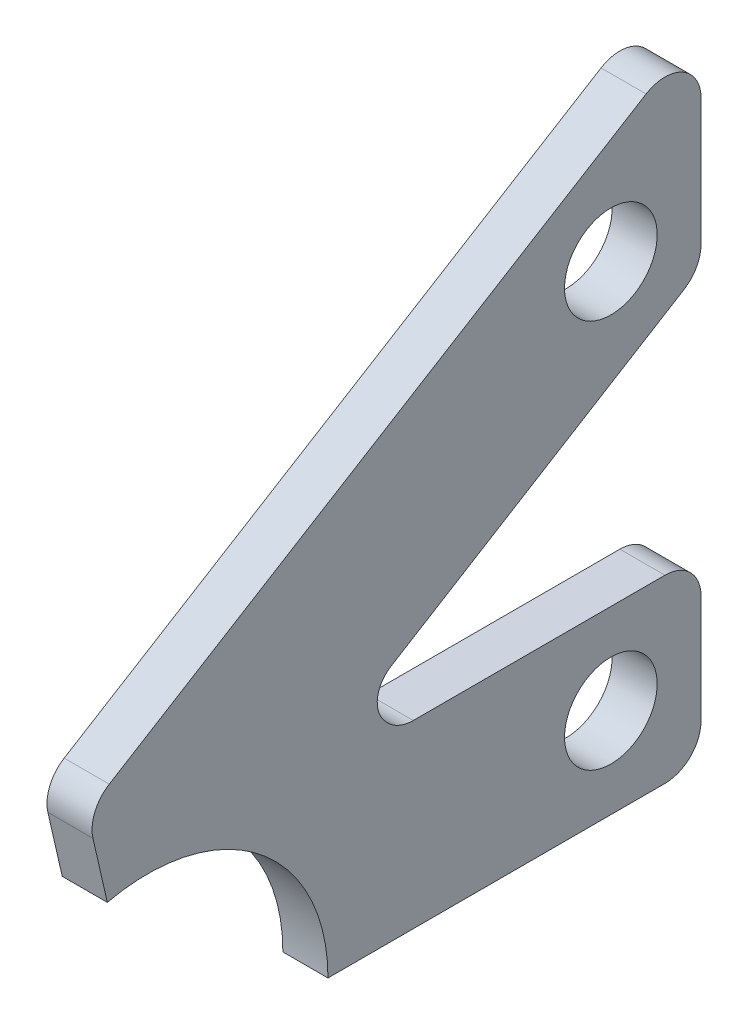
SolidWorks part; units mm, degrees
material "AISI 4130 Steel, annealed at 865C"
ref_plane "Front Plane" through (0, 0, 0) normal (0, 0, 1) x (1, 0, 0)
ref_plane "Top Plane" through (0, 0, 0) normal (0, 1, 0) x (1, 0, 0)
ref_plane "Right Plane" through (0, 0, 0) normal (1, 0, 0) x (0, 0, -1)
sketch "Sketch2" plane through (-112.555, 0, -573.5897) normal (-1, 0, 0) x (0, 0.6231, 0.7821)
  line L0 (845.7718, 136.9996) -> (864.3306, 122.2137)
  line L1 (871.0899, 172.8543) -> (811.2713, 97.7721) construction
  line L2 (864.3306, 122.2137) -> (884.1965, 122.2137) construction
  line L3 (884.1965, 122.2137) -> (887.7358, 125.0335)
  line L4 (853.6855, 146.9326) -> (867.5451, 135.8905)
  line L5 (888.541, 127.8859) -> (873.4237, 169.576)
  line L6 (871.3239, 138.1115) -> (863.0777, 160.8527)
  line L7 (845.3679, 140.569) -> (850.1161, 146.5287)
  line L8 (863.479, 163.3013) -> (869.0493, 170.2929)
  line L9 (852.7085, 139.592) -> (869.7744, 161.0125) construction
  circle A0 centre (874.2635, 114.3) radius 12.7 construction
  arc A1 (864.3306, 122.2137) -> (884.1965, 122.2137) centre (874.2635, 114.3) cw
  arc A2 (887.7358, 125.0335) -> (888.541, 127.8859) centre (886.1531, 127.0201) ccw
  circle A3 centre (852.7085, 139.592) radius 3.2639
  circle A4 centre (869.7744, 161.0125) radius 3.2639
  arc A6 (869.8308, 135.4301) -> (869.6684, 135.3953) centre (874.2635, 114.3) ccw
  arc A7 (845.7718, 136.9996) -> (845.3679, 140.569) centre (847.3545, 138.9862) cw
  arc A8 (853.6855, 146.9326) -> (850.1161, 146.5287) centre (852.1027, 144.946) ccw
  arc A9 (869.0493, 170.2929) -> (873.4237, 169.576) centre (871.0358, 168.7102) cw
  arc A10 (863.0777, 160.8527) -> (863.479, 163.3013) centre (865.4656, 161.7186) cw
  arc A11 (867.5451, 135.8905) -> (869.6684, 135.3953) centre (869.1278, 137.8771) ccw
  arc A12 (871.3239, 138.1115) -> (869.8308, 135.4301) centre (869.4136, 137.4188) cw
  point P17 (889.163, 126.1705)
  point P25 (843.7852, 138.5824)
  point P28 (851.6989, 148.5153)
  point P31 (871.8768, 173.842)
  point P34 (862.593, 162.1893)
  dimension "D5" = 2.54
  dimension "D10" = 6.5278
  dimension "D9" = 2.54
  dimension "D4" = 8.89
  dimension "D12" = 2.54
  dimension "D13" = 2.54
  dimension "D14" = 2.54
  dimension "D15" = 2.54
  dimension "D16" = 2.032
  dimension "D1" = 12.7
  dimension "D2" = 12.7
  dimension "D3" = 6.35
  dimension "D7" = 6.35
  dimension "D8" = 6.35
  dimension "D11" = 6.35
extrude "Boss-Extrude1" add sketch "Sketch2" along normal blind 3.175
ref_plane "Plane1" through (0, 375.1306, -298.8699) normal (0, -0.7821, 0.6231) x (-1, 0, 0)
